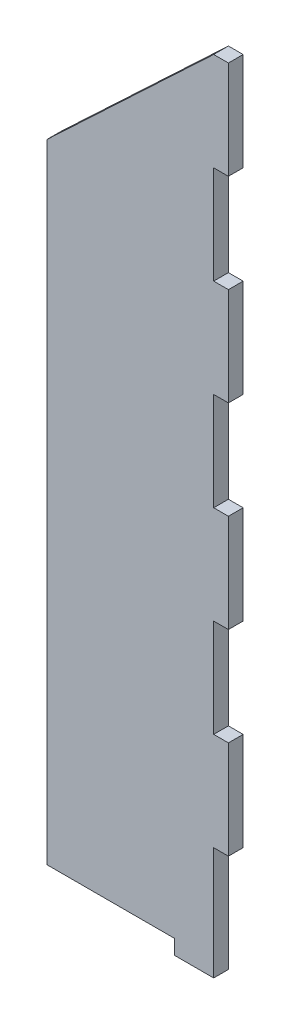
SolidWorks part; units mm, degrees
ref_plane "Front Plane" through (0, 0, 0) normal (0, 0, 1) x (1, 0, 0)
ref_plane "Top Plane" through (0, 0, 0) normal (0, 1, 0) x (1, 0, 0)
ref_plane "Right Plane" through (0, 0, 0) normal (1, 0, 0) x (0, 0, -1)
sketch "Sketch1" plane through (0, 0, 0) normal (0, 0, 1) x (1, 0, 0)
  line L0 (-26.9875, -101.6) -> (-26.9875, 101.6)
  line L1 (-26.9875, 101.6) -> (26.9875, 152.4)
  line L2 (26.9875, 152.4) -> (26.9875, -101.6)
  line L3 (26.9875, -101.6) -> (-26.9875, -101.6)
  line L4 (-26.9875, 0) -> (26.9875, 0) construction
  line L5 (26.9875, 120.65) -> (26.9875, 88.9)
  line L6 (26.9875, 152.4) -> (31.75, 152.4)
  line L7 (26.9875, 152.4) -> (26.9875, 120.65)
  line L8 (26.9875, 120.65) -> (31.75, 120.65)
  line L9 (31.75, 152.4) -> (31.75, 120.65)
  line L10 (26.9875, 120.65) -> (31.75, 120.65)
  line L11 (31.75, 120.65) -> (31.75, 88.9)
  line L12 (26.9875, 88.9) -> (31.75, 88.9)
  line L13 (26.9875, 88.9) -> (26.9875, 57.15)
  line L14 (26.9875, 88.9) -> (31.75, 88.9)
  line L15 (31.75, 88.9) -> (31.75, 57.15)
  line L16 (26.9875, 57.15) -> (31.75, 57.15)
  line L17 (26.9875, 57.15) -> (26.9875, 25.4)
  line L18 (26.9875, 57.15) -> (31.75, 57.15)
  line L19 (31.75, 57.15) -> (31.75, 25.4)
  line L20 (26.9875, 25.4) -> (31.75, 25.4)
  line L21 (26.9875, 25.4) -> (26.9875, -6.35)
  line L22 (26.9875, 25.4) -> (31.75, 25.4)
  line L23 (31.75, 25.4) -> (31.75, -6.35)
  line L24 (26.9875, -6.35) -> (31.75, -6.35)
  line L25 (26.9875, -6.35) -> (26.9875, -38.1)
  line L26 (26.9875, -6.35) -> (31.75, -6.35)
  line L27 (31.75, -6.35) -> (31.75, -38.1)
  line L28 (26.9875, -38.1) -> (31.75, -38.1)
  line L29 (26.9875, -38.1) -> (26.9875, -69.85)
  line L30 (26.9875, -38.1) -> (31.75, -38.1)
  line L31 (31.75, -38.1) -> (31.75, -69.85)
  line L32 (26.9875, -69.85) -> (31.75, -69.85)
  line L33 (26.9875, -69.85) -> (26.9875, -101.6)
  line L42 (26.9875, -69.85) -> (31.75, -69.85)
  line L43 (31.75, -69.85) -> (31.75, -101.6)
  line L44 (26.9875, -101.6) -> (31.75, -101.6)
  line L46 (14.2875, -101.6) -> (26.9875, -101.6)
  line L47 (14.2875, -101.6) -> (14.2875, -106.3625)
  line L48 (14.2875, -106.3625) -> (26.9875, -106.3625)
  line L49 (26.9875, -101.6) -> (26.9875, -106.3625)
  point P2 (0, 0)
  dimension "D1" = 53.975
  dimension "D2" = 254
  dimension "D3" = 203.2
  dimension "D4" = 4.7625
  dimension "D6" = 31.75
  dimension "D7" = 12.7
  dimension "D8" = 4.7625
  dimension "D5" = 8
extrude "Boss-Extrude1" add sketch "Sketch1" along normal blind 4.7625 contours L4 L0 L3 L2 L21 | L0 L4 L2 L1 | L9 L6 L2 L8 | L2 L16 L15 L12 | L2 L21 L24 L23 L20 | L2 L32 L31 L28 | L32 L3 L47 region at (0, -50.8, 0) region at (1.7992, 64.3467, 0) region at (20.6375, -103.9813, 0) region at (29.3688, 9.525, 0) region at (29.3688, 136.525, 0) region at (29.3688, -53.975, 0) region at (29.3688, 73.025, 0)
equation "\"Height\"= 12in"
equation "\"Depth\"= 7in"
equation "\"WallThickness\"= 0.1875in"
equation "\"FloorThickness\"= 0.1875in"
equation "\"D1@Sketch1\"=(\"Depth\"-2.75)/2"
equation "\"D4@Sketch1\"=\"WallThickness\""
equation "\"D6@Sketch1\"=\"D2@Sketch1\"/\"D5@Sketch1\""
equation "\"D8@Sketch1\"=\"FloorThickness\""
equation "\"D1@Boss-Extrude1\"=\"WallThickness\""
equation "\"Width\" = 30in"
